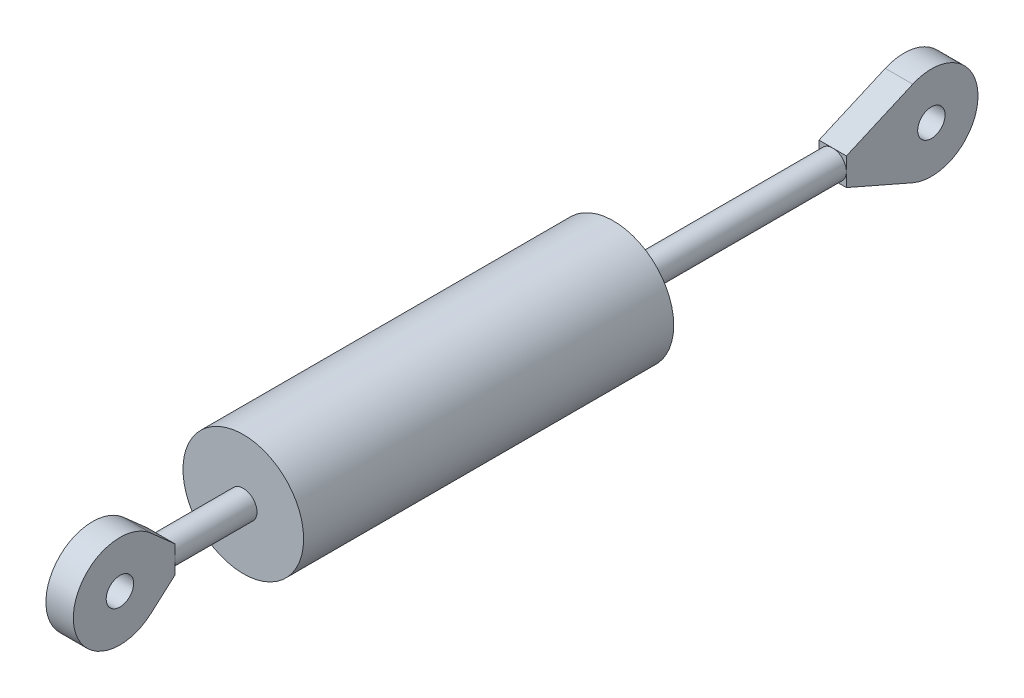
SolidWorks part; units mm, degrees
ref_plane "Front Plane" through (0, 0, 0) normal (0, 0, 1) x (1, 0, 0)
ref_plane "Top Plane" through (0, 0, 0) normal (0, 1, 0) x (1, 0, 0)
ref_plane "Right Plane" through (0, 0, 0) normal (1, 0, 0) x (0, 0, -1)
sketch "Sketch1" plane through (0, 0, 0) normal (1, 0, 0) x (0, 0, -1)
  line L0 (-34.5921, 0) -> (32.9079, 0)
  line L1 (-34.5921, 11) -> (32.9079, 11)
  line L2 (-34.5921, 11) -> (-34.5921, 0)
  line L4 (32.9079, 11) -> (32.9079, 0)
  line L5 (-34.5921, 11) -> (0, 0) construction
  line L6 (0, 0) -> (32.9079, 11) construction
  point P0 (0, 0)
  dimension "D1" = 67.5
  dimension "D2" = 11
revolve "Revolve1" add sketch "Sketch1" angle 360 about L0
sketch "Sketch2" plane through (0, 0, 34.5921) normal (0, 0, 1) x (1, 0, 0)
  circle A0 centre (0, 0) radius 2.5
  dimension "D1" = 5
extrude "Boss-Extrude1" add sketch "Sketch2" along normal blind 15
sketch "Sketch3" plane through (0, 0, 0) normal (1, 0, 0) x (0, 0, -1)
  line L0 (-34.5921, 11) -> (-34.5921, -11) construction
  line L1 (-49.5921, 2.5) -> (-53.9583, 6.3648)
  line L2 (-49.5921, -2.5) -> (-53.9583, -6.3648)
  line L3 (-49.5921, 2.5) -> (-49.5921, -2.5)
  arc A0 (-53.9583, 6.3648) -> (-53.9583, -6.3648) centre (-59.5921, 0) ccw
  circle A1 centre (-59.5921, 0) radius 2.5
  dimension "D1" = 17
  dimension "D2" = 5
  dimension "D3" = 25
extrude "Boss-Extrude2" add sketch "Sketch3" along normal blind 2.5 and the other way blind 2.5
sketch "Sketch4" plane through (0, 0, -32.9079) normal (0, 0, -1) x (-1, 0, 0)
  circle A0 centre (0, 0) radius 2.5
  dimension "D1" = 5
extrude "Boss-Extrude3" add sketch "Sketch4" along normal blind 40
sketch "Sketch5" plane through (0, 0, 0) normal (1, 0, 0) x (0, 0, -1)
  line L4 (32.9079, -11) -> (32.9079, 11) construction
  line L5 (0, 0) -> (112.0554, 0) construction
  line L6 (72.9079, 2.5) -> (85.0028, 7.7881)
  line L7 (72.9079, 2.5) -> (72.9079, -2.5)
  line L8 (72.9079, -2.5) -> (85.0028, -7.7881)
  circle A1 centre (88.4079, 0) radius 2.5
  arc A2 (85.0028, -7.7881) -> (85.0028, 7.7881) centre (88.4079, 0) ccw
  dimension "D1" = 8.5
  dimension "D2" = 5
  dimension "D3" = 55.5
extrude "Boss-Extrude4" add sketch "Sketch5" along normal blind 2.5 and the other way blind 2.5
